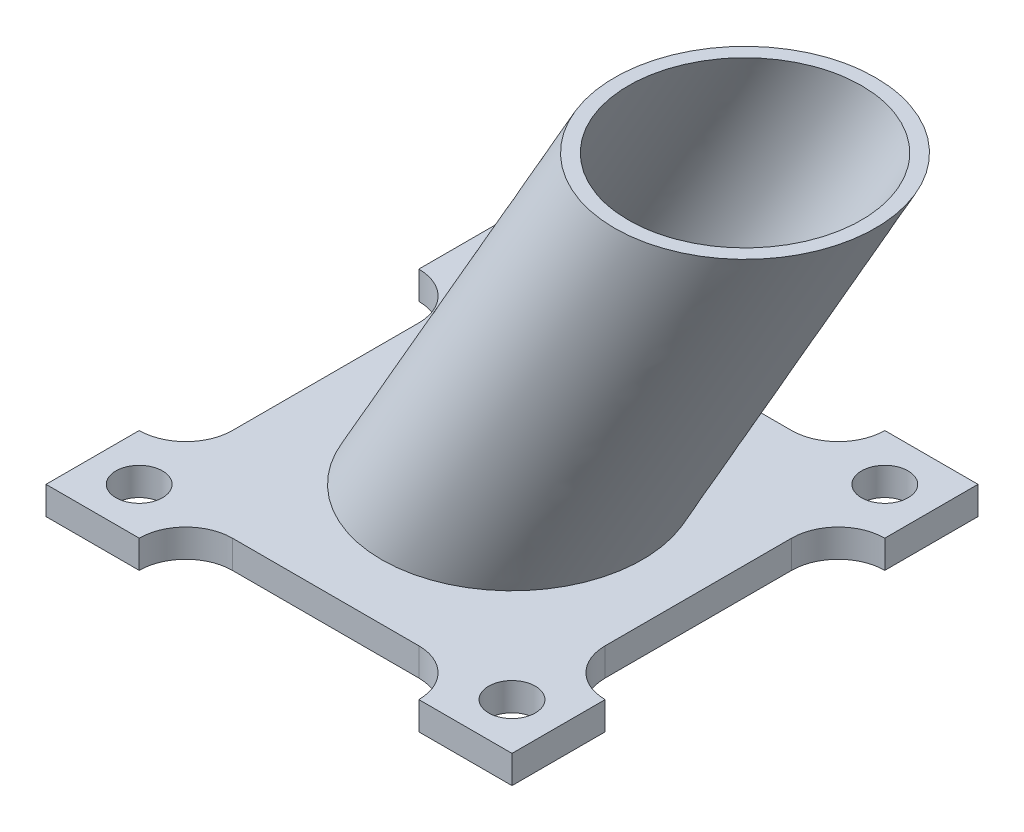
SolidWorks part; units mm, degrees
ref_plane "Front Plane" through (0, 0, 0) normal (0, 0, 1) x (1, 0, 0)
ref_plane "Top Plane" through (0, 0, 0) normal (0, 1, 0) x (1, 0, 0)
ref_plane "Right Plane" through (0, 0, 0) normal (1, 0, 0) x (0, 0, -1)
sketch "Sketch1" plane through (0, 0, 0) normal (0, 1, 0) x (1, 0, 0)
  line L1 (-25, 25) -> (25, 25)
  line L2 (-25, 25) -> (-25, -25)
  line L3 (-25, -25) -> (25, -25)
  line L4 (25, 25) -> (25, -25)
  line L5 (-25, 25) -> (25, -25) construction
  line L6 (-25, -25) -> (25, 25) construction
  dimension "D1" = 50
  dimension "D2" = 50
extrude "Boss-Extrude1" add sketch "Sketch1" along normal blind 3
sketch "Sketch2" plane through (0, 0, 0) normal (0, 0, 1) x (1, 0, 0)
  line L0 (0, 3) -> (25, 46.3013)
  line L1 (-25, 3) -> (25, 3) construction
  line L2 (0, -11.0306) -> (0, 11.0306) construction
  dimension "D1" = 60
  dimension "D2" = 50
sketch "Sketch3" plane through (0, 3, 0) normal (0, 1, 0) x (1, 0, 0)
  circle A0 centre (0, 0) radius 14
  circle A1 centre (0, 0) radius 12.5
  dimension "D1" = 25
  dimension "D2" = 28
sweep "Sweep1" add profiles "Sketch3" path "Sketch2"
sketch "Sketch4" plane through (0, 3, 0) normal (0, 1, 0) x (1, 0, 0)
  line L0 (-25.4657, 0) -> (25.4657, 0) construction
  line L2 (0, -25.4657) -> (0, 25.4657) construction
  circle A0 centre (-20, 20) radius 2.5
  circle A1 centre (20, 20) radius 2.5
  circle A2 centre (20, -20) radius 2.5
  circle A3 centre (-20, -20) radius 2.5
  dimension "D1" = 5
  dimension "D2" = 20
  dimension "D3" = 20
  dimension "D4" = 20
extrude "Cut-Extrude1" cut sketch "Sketch4" against normal up to next
sketch "Sketch5" plane through (0, 3, 0) normal (0, 1, 0) x (1, 0, 0)
  line L0 (-10, 25) -> (10, 25) construction
  line L1 (-10, 30) -> (10, 30)
  line L2 (-10, 20) -> (10, 20)
  line L3 (0, -25.4657) -> (0, 25.4657) construction
  line L8 (25, 25) -> (-25, 25) construction
  arc A0 (-10, 30) -> (-10, 20) centre (-10, 25) ccw
  arc A1 (10, 20) -> (10, 30) centre (10, 25) ccw
  point P2 (0, 25)
  dimension "D1" = 10
  dimension "D2" = 10
  dimension "D3" = 20
  dimension "D4" = 10
extrude "Cut-Extrude2" cut sketch "Sketch5" against normal up to next
ref_axis "Axis1" through (0, 86.4299, 0) along (0, -1, 0)
pattern_circular "CirPattern1" count 4 over 360 about axis through (0, 86.4299, 0) along (0, -1, 0) of "Cut-Extrude2"
